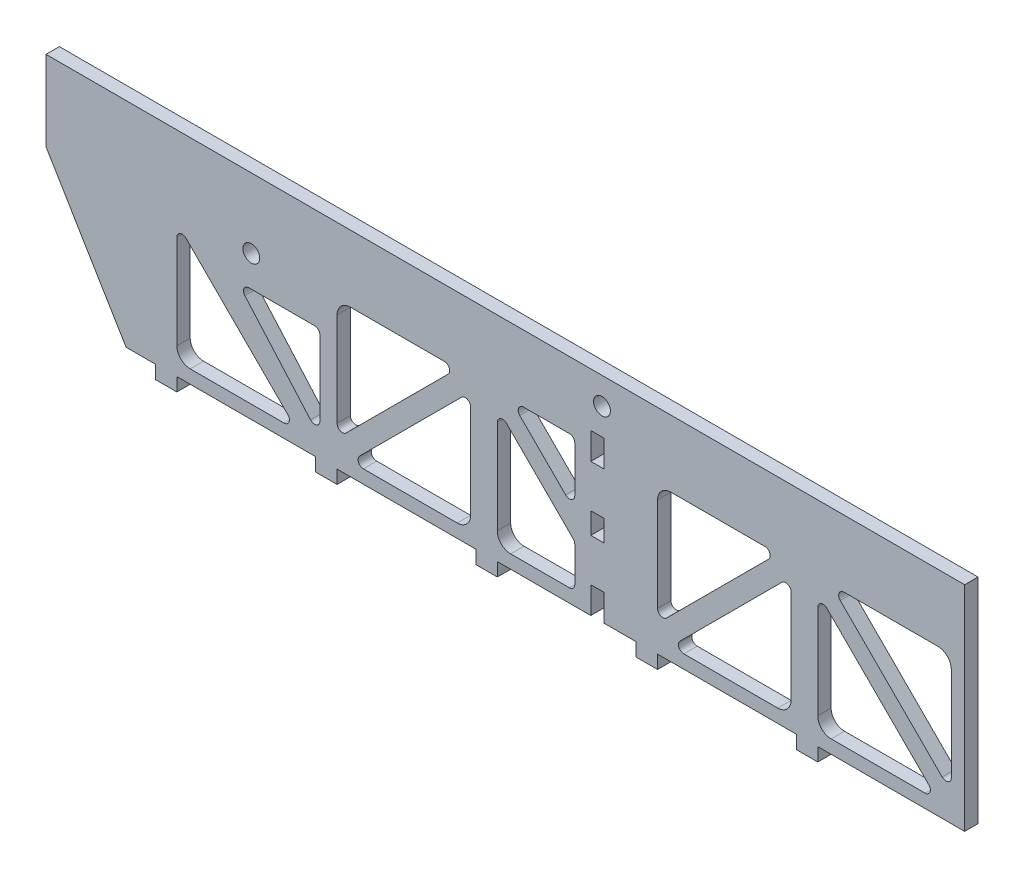
SolidWorks part; units mm, degrees
material "Pine"
ref_plane "Front Plane" through (0, 0, 0) normal (0, 0, 1) x (1, 0, 0)
ref_plane "Top Plane" through (0, 0, 0) normal (0, 1, 0) x (1, 0, 0)
ref_plane "Right Plane" through (0, 0, 0) normal (1, 0, 0) x (0, 0, -1)
sketch "Model" plane through (0, 0, 0) normal (0, 0, 1) x (1, 0, 0)
  line L0 (-306.6281, 15.625) -> (-306.6281, 51.1493)
  line L1 (-309.1681, 53.6893) -> (-340.406, 53.6893)
  line L2 (-342.3135, 49.472) -> (-311.0755, 13.9477)
  line L8 (-171.2321, 6.35) -> (-215.9, 6.35)
  line L9 (-222.25, 57.3679) -> (-222.25, 12.7)
  line L10 (-217.9139, 59.1639) -> (-169.4361, 10.6861)
  line L11 (-234.95, 57.3679) -> (-234.95, 12.7)
  line L12 (-241.3, 6.35) -> (-285.9679, 6.35)
  line L13 (-239.2861, 59.1639) -> (-287.7639, 10.6861)
  line L14 (-294.1139, 17.0361) -> (-245.6361, 65.5139)
  line L15 (-298.45, 63.5) -> (-298.45, 18.8321)
  line L16 (-247.4321, 69.85) -> (-292.1, 69.85)
  line L17 (-323.6321, 6.35) -> (-368.3, 6.35)
  line L18 (-374.65, 57.3679) -> (-374.65, 12.7)
  line L19 (-370.3139, 59.1639) -> (-321.8361, 10.6861)
  line L20 (-18.8321, 6.35) -> (-63.5, 6.35)
  line L21 (-69.85, 57.3679) -> (-69.85, 12.7)
  line L22 (-17.0361, 10.6861) -> (-65.5139, 59.1639)
  line L23 (-82.55, 57.3679) -> (-82.55, 12.7)
  line L24 (-88.9, 6.35) -> (-133.5679, 6.35)
  line L25 (-86.8861, 59.1639) -> (-135.3639, 10.6861)
  line L26 (-93.2361, 65.5139) -> (-141.7139, 17.0361)
  line L27 (-146.05, 63.5) -> (-146.05, 18.8321)
  line L28 (-95.0321, 69.85) -> (-139.7, 69.85)
  line L29 (-163.0861, 17.0361) -> (-211.5639, 65.5139)
  line L30 (-165.1, 69.85) -> (-209.7679, 69.85)
  line L31 (-158.75, 63.5) -> (-158.75, 18.8321)
  line L35 (-398.78, 0) -> (-436.88, 63.5)
  line L36 (0, 0) -> (-398.78, 0)
  line L37 (0, 0) -> (0, 95.25)
  line L38 (0, 95.25) -> (-436.88, 95.25)
  line L39 (-436.88, 63.5) -> (-436.88, 95.25)
  line L40 (-6.35, 63.5) -> (-6.35, 18.8321)
  line L41 (-59.1639, 65.5139) -> (-10.6861, 17.0361)
  line L42 (-12.7, 69.85) -> (-57.3679, 69.85)
  arc A0 (-222.25, 12.7) -> (-215.9, 6.35) centre (-215.9, 12.7) ccw
  arc A1 (-217.9139, 59.1639) -> (-222.25, 57.3679) centre (-219.71, 57.3679) ccw
  arc A2 (-171.2321, 6.35) -> (-169.4361, 10.6861) centre (-171.2321, 8.89) ccw
  arc A3 (-234.95, 57.3679) -> (-239.2861, 59.1639) centre (-237.49, 57.3679) ccw
  arc A4 (-241.3, 6.35) -> (-234.95, 12.7) centre (-241.3, 12.7) ccw
  arc A5 (-287.7639, 10.6861) -> (-285.9679, 6.35) centre (-285.9679, 8.89) ccw
  arc A6 (-245.6361, 65.5139) -> (-247.4321, 69.85) centre (-247.4321, 67.31) ccw
  arc A7 (-298.45, 18.8321) -> (-294.1139, 17.0361) centre (-295.91, 18.8321) ccw
  arc A8 (-292.1, 69.85) -> (-298.45, 63.5) centre (-292.1, 63.5) ccw
  arc A9 (-323.6321, 6.35) -> (-321.8361, 10.6861) centre (-323.6321, 8.89) ccw
  arc A10 (-374.65, 12.7) -> (-368.3, 6.35) centre (-368.3, 12.7) ccw
  arc A11 (-370.3139, 59.1639) -> (-374.65, 57.3679) centre (-372.11, 57.3679) ccw
  arc A12 (-69.85, 12.7) -> (-63.5, 6.35) centre (-63.5, 12.7) ccw
  arc A13 (-65.5139, 59.1639) -> (-69.85, 57.3679) centre (-67.31, 57.3679) ccw
  arc A14 (-18.8321, 6.35) -> (-17.0361, 10.6861) centre (-18.8321, 8.89) ccw
  arc A15 (-82.55, 57.3679) -> (-86.8861, 59.1639) centre (-85.09, 57.3679) ccw
  arc A16 (-88.9, 6.35) -> (-82.55, 12.7) centre (-88.9, 12.7) ccw
  arc A17 (-135.3639, 10.6861) -> (-133.5679, 6.35) centre (-133.5679, 8.89) ccw
  arc A18 (-93.2361, 65.5139) -> (-95.0321, 69.85) centre (-95.0321, 67.31) ccw
  arc A19 (-146.05, 18.8321) -> (-141.7139, 17.0361) centre (-143.51, 18.8321) ccw
  arc A20 (-139.7, 69.85) -> (-146.05, 63.5) centre (-139.7, 63.5) ccw
  arc A21 (-163.0861, 17.0361) -> (-158.75, 18.8321) centre (-161.29, 18.8321) ccw
  arc A22 (-209.7679, 69.85) -> (-211.5639, 65.5139) centre (-209.7679, 67.31) ccw
  arc A23 (-158.75, 63.5) -> (-165.1, 69.85) centre (-165.1, 63.5) ccw
  arc A24 (-306.6281, 15.625) -> (-311.0755, 13.9477) centre (-309.1681, 15.625) cw
  arc A25 (-340.406, 53.6893) -> (-342.3135, 49.472) centre (-340.406, 51.1493) ccw
  arc A26 (-306.6281, 51.1493) -> (-309.1681, 53.6893) centre (-309.1681, 51.1493) ccw
  arc A27 (-10.6861, 17.0361) -> (-6.35, 18.8321) centre (-8.89, 18.8321) ccw
  arc A28 (-57.3679, 69.85) -> (-59.1639, 65.5139) centre (-57.3679, 67.31) ccw
  arc A29 (-6.35, 63.5) -> (-12.7, 69.85) centre (-12.7, 63.5) ccw
  circle A30 centre (-172.466, 88.9) radius 4
  circle A31 centre (-339.2348, 68.4233) radius 4
  dimension "D2" = 172.466
  dimension "D4" = 8
  dimension "D5" = 166.7688
  dimension "D7" = 8
  dimension "D6" = 20.4767
  dimension "D8" = 2.54
  dimension "D1" = 95.25
  dimension "D3" = 6.35
extrude "Boss-Extrude1" add sketch "Model" along normal blind 6.35
sketch "Sketch1" plane through (0, 0, 6.35) normal (0, 0, 1) x (1, 0, 0)
  line L0 (-69.85, 95.25) -> (-69.85, 0) construction
  line L1 (-69.85, 57.3679) -> (-69.85, 12.7) construction
  line L2 (-398.78, 0) -> (0, 0) construction
  line L3 (-146.05, 95.25) -> (-146.05, 0) construction
  line L4 (-146.05, 63.5) -> (-146.05, 18.8321) construction
  line L5 (-222.25, 95.25) -> (-222.25, 0) construction
  line L6 (-222.25, 57.3679) -> (-222.25, 12.7) construction
  line L7 (-298.45, 95.25) -> (-298.45, 0) construction
  line L8 (-298.45, 63.5) -> (-298.45, 18.8321) construction
  line L9 (-374.65, 95.25) -> (-374.65, 0) construction
  line L10 (-374.65, 57.3679) -> (-374.65, 12.7) construction
  line L11 (0, 95.25) -> (-436.88, 95.25) construction
  line L12 (-69.85, 0) -> (-80.01, 0)
  line L13 (-69.85, 0) -> (-69.85, -6.35)
  line L14 (-69.85, -6.35) -> (-80.01, -6.35)
  line L15 (-80.01, 0) -> (-80.01, -6.35)
  line L16 (-146.05, 0) -> (-156.21, 0)
  line L17 (-146.05, 0) -> (-146.05, -6.35)
  line L18 (-146.05, -6.35) -> (-156.21, -6.35)
  line L19 (-156.21, 0) -> (-156.21, -6.35)
  line L20 (-222.25, 0) -> (-232.41, 0)
  line L21 (-222.25, 0) -> (-222.25, -6.35)
  line L22 (-222.25, -6.35) -> (-232.41, -6.35)
  line L23 (-232.41, 0) -> (-232.41, -6.35)
  line L24 (-298.45, 0) -> (-308.61, 0)
  line L25 (-298.45, 0) -> (-298.45, -6.35)
  line L26 (-298.45, -6.35) -> (-308.61, -6.35)
  line L27 (-308.61, 0) -> (-308.61, -6.35)
  line L28 (-374.65, 0) -> (-384.81, 0)
  line L29 (-374.65, 0) -> (-374.65, -6.35)
  line L30 (-374.65, -6.35) -> (-384.81, -6.35)
  line L31 (-384.81, 0) -> (-384.81, -6.35)
  line L32 (0, 0) -> (0, 95.25) construction
  line L53 (-436.88, 95.25) -> (0, 95.25)
  line L54 (-436.88, 95.25) -> (-436.88, 101.6)
  line L55 (-436.88, 101.6) -> (0, 101.6)
  line L56 (0, 95.25) -> (0, 101.6)
  dimension "D1" = 6.35
  dimension "D2" = 10.16
  dimension "D3" = 10.16
  dimension "D4" = 10.16
  dimension "D5" = 10.16
  dimension "D6" = 10.16
  dimension "D8" = 6.35
extrude "Boss-Extrude2" add sketch "Sketch1" against normal up to surface (6.35 mm away) up to face at (-168.466, 88.9, 0)
sketch "Sketch2" plane through (0, 0, 0) normal (0, 0, -1) x (-1, 0, 0)
  line L0 (158.75, 18.8321) -> (158.75, 63.5) construction
  line L1 (185.42, 69.85) -> (165.1, 69.85)
  line L2 (185.42, 69.85) -> (185.42, 0)
  line L3 (185.42, 0) -> (165.1, 0)
  line L4 (165.1, 69.85) -> (165.1, 0)
  line L6 (222.25, 0) -> (156.21, 0) construction
  line L8 (165.1, 69.85) -> (209.7679, 69.85) construction
  line L10 (156.21, -6.35) -> (146.05, -6.35) construction
  line L11 (177.8, 0) -> (171.45, 0)
  line L12 (177.8, 0) -> (177.8, 12.7)
  line L13 (177.8, 12.7) -> (171.45, 12.7)
  line L14 (171.45, 0) -> (171.45, 12.7)
  line L15 (177.8, 33.02) -> (171.45, 33.02)
  line L16 (177.8, 33.02) -> (177.8, 43.18)
  line L17 (177.8, 43.18) -> (171.45, 43.18)
  line L18 (171.45, 33.02) -> (171.45, 43.18)
  line L19 (177.8, 63.5) -> (171.45, 63.5)
  line L20 (177.8, 63.5) -> (177.8, 76.2)
  line L21 (177.8, 76.2) -> (171.45, 76.2)
  line L22 (171.45, 63.5) -> (171.45, 76.2)
  dimension "D1" = 6.35
  dimension "D2" = 20.32
  dimension "D3" = 10.16
  dimension "D4" = 12.7
  dimension "D5" = 6.35
  dimension "D6" = 20.32
  dimension "D7" = 20.32
  dimension "D8" = 12.7
  dimension "D9" = 6.35
  dimension "D10" = 6.35
extrude "Boss-Extrude3" add sketch "Sketch2" against normal up to surface (6.35 mm away) contours L4 | L19 L22 L1 L4 L3 L14 L13 L12 L2 L20 L15 L18 L17 L16 region at (-184.6925, 34.925, 0) up to face at (-319.4123, 39.5294, 6.35)
extrude "Cut-Extrude1" cut sketch "Sketch2<3>" against normal blind 6.35 contours L22 L1 L20 L21 | L14 L3 L12 L13 region at (-174.625, 73.025, 0) region at (-174.625, 6.35, 0)
sketch "Sketch2<3>" plane through (0, 0, 0) normal (0, 0, -1) x (-1, 0, 0) same geometry as "Sketch2"
sketch "Sketch3" plane through (0, 0, 0) normal (0, 0, -1) x (-1, 0, 0)
  line L1 (154.4024, 72.7027) -> (167.3891, 72.7027)
  line L2 (154.4024, 72.7027) -> (154.4024, 13.591)
  line L3 (154.4024, 13.591) -> (167.3891, 13.591)
  line L4 (167.3891, 72.7027) -> (167.3891, 13.591)
extrude "Boss-Extrude4" add sketch "Sketch3" against normal up to surface (6.35 mm away) up to face at (-224.7462, 7.8828, 6.35)
sketch "Sketch4" plane through (0, 0, 6.35) normal (0, 0, 1) x (1, 0, 0)
  line L0 (-185.42, 69.85) -> (-209.7679, 69.85) construction
  line L1 (-185.42, 39.37) -> (-185.42, 69.85) construction
  line L2 (-211.5639, 65.5139) -> (-185.42, 39.37) construction
  line L3 (-185.42, 26.67) -> (-217.9139, 59.1639) construction
  line L4 (-185.42, 6.35) -> (-185.42, 26.67) construction
  line L5 (-215.9, 6.35) -> (-185.42, 6.35) construction
  line L6 (-187.96, 69.85) -> (-209.7679, 69.85)
  line L7 (-185.42, 45.5021) -> (-185.42, 67.31)
  line L8 (-211.5639, 65.5139) -> (-189.7561, 43.7061)
  line L9 (-186.1639, 27.4139) -> (-217.9139, 59.1639)
  line L10 (-185.42, 8.89) -> (-185.42, 25.6179)
  line L11 (-215.9, 6.35) -> (-187.96, 6.35)
  line L12 (-187.96, 6.35) -> (-185.42, 6.35)
  line L13 (-185.42, 6.35) -> (-185.42, 8.89)
  line L14 (-185.42, 25.6179) -> (-185.42, 26.67)
  line L15 (-185.42, 26.67) -> (-186.1639, 27.4139)
  line L16 (-185.42, 45.5021) -> (-185.42, 39.37)
  line L17 (-185.42, 39.37) -> (-189.7561, 43.7061)
  line L18 (-187.96, 69.85) -> (-185.42, 69.85)
  line L19 (-185.42, 69.85) -> (-185.42, 67.31)
  arc A0 (-187.96, 69.85) -> (-185.42, 67.31) centre (-187.96, 67.31) cw
  arc A1 (-185.42, 45.5021) -> (-189.7561, 43.7061) centre (-187.96, 45.5021) cw
  arc A2 (-186.1639, 27.4139) -> (-185.42, 25.6179) centre (-187.96, 25.6179) cw
  arc A3 (-187.96, 6.35) -> (-185.42, 8.89) centre (-187.96, 8.89) ccw
  dimension "D1" = 2.54
extrude "Boss-Extrude6" add sketch "Sketch4" against normal up to surface (6.35 mm away) contours A3 L12 L13 | L15 A2 L14 | L16 A1 L17 | L18 A0 L19 region at (-185.9874, 69.2826, 6.35) region at (-186.5486, 42.0946, 6.35) region at (-185.5728, 26.6067, 6.35) region at (-185.9874, 6.9174, 6.35) up to face at (-208.5115, 28.1226, 0)
equation "\"thick\"=0.25"
equation "\"D1@Boss-Extrude1\"=\"thick\""
